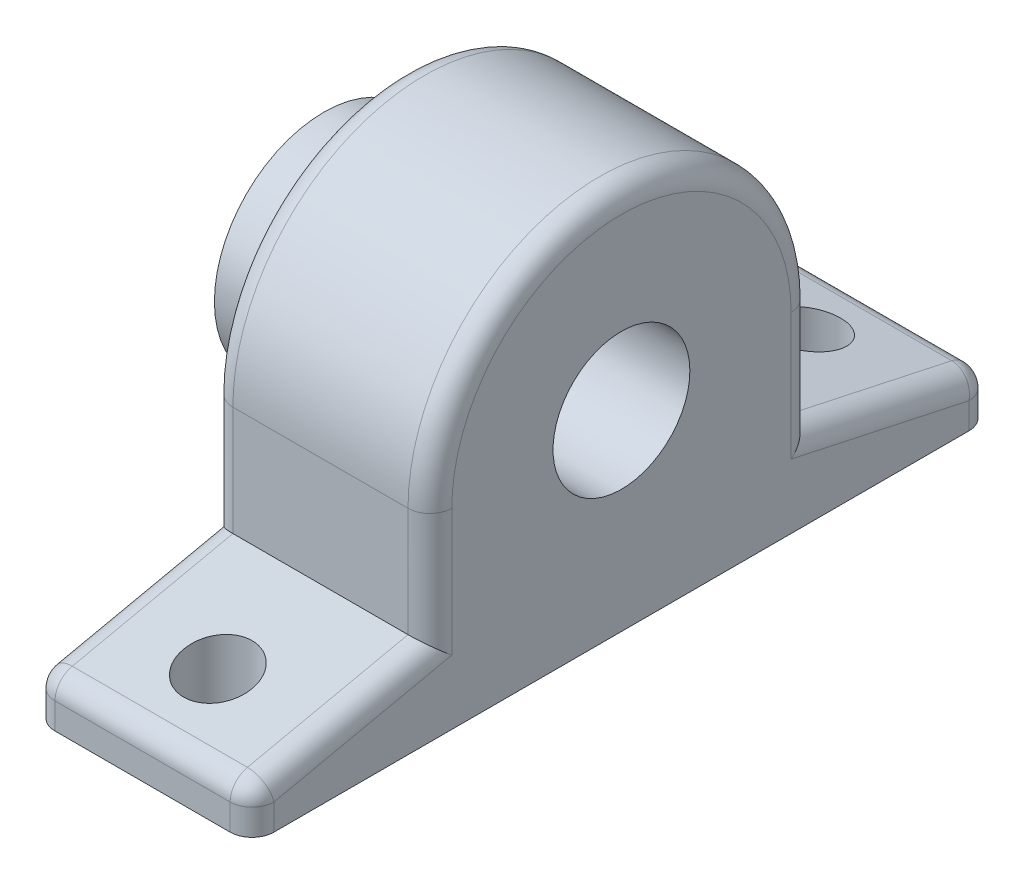
SolidWorks part; units mm, degrees
material "AISI 1020"
ref_plane "Front Plane" through (0, 0, 0) normal (0, 0, 1) x (1, 0, 0)
ref_plane "Top Plane" through (0, 0, 0) normal (0, 1, 0) x (1, 0, 0)
ref_plane "Right Plane" through (0, 0, 0) normal (1, 0, 0) x (0, 0, -1)
sketch "Sketch1" plane through (0, 0, 0) normal (1, 0, 0) x (0, 0, -1)
  line L0 (22.225, 0) -> (22.225, -12.7)
  line L1 (-42.8625, -22.225) -> (42.8625, -22.225)
  line L3 (22.225, -12.7) -> (22.2011, -13.0472)
  line L4 (-22.225, 0) -> (-22.225, -12.7)
  line L5 (42.8625, -22.225) -> (42.8625, -17.145)
  line L6 (-42.8625, -22.225) -> (-42.8625, -17.145)
  line L7 (-42.8625, -17.145) -> (-22.225, -12.7)
  line L8 (22.225, -12.7) -> (42.8625, -17.145)
  line L9 (42.8625, -17.145) -> (43.2049, -17.2391)
  arc A1 (-22.225, 0) -> (22.225, 0) centre (0, 0) cw
extrude "Extrude1" add sketch "Sketch1" along normal blind 25.4
sketch "Sketch2" plane through (25.4, 0, 0) normal (1, 0, 0) x (0, 0, -1)
  circle A0 centre (0, 0) radius 7.9375
extrude "Cut-Extrude1" cut sketch "Sketch2" against normal blind 25.4
fillet "Fillet1" radius 2.54 1 edges at (25.4, -14.9225, 32.5437)
fillet "Fillet2" radius 2.54 3 edges at (25.4, -20.9841, 42.8625) (24.6561, -17.906, 42.8625) (11.43, -17.145, 42.8625)
fillet "Fillet3" radius 2.54 3 edges at (25.4, -6.35, -22.225) (25.4, 22.225, 0) (25.4, -7.6491, 22.225)
fillet "Fillet4" radius 2.54 3 edges at (0, -6.35, 22.225) (0, -6.35, -22.225) (0, 22.225, 0)
fillet "Fillet5" radius 2.54 3 edges at (0, -20.7106, 42.8625) (0, -17.6004, 42.2986) (0, -14.433, 30.2712)
fillet "Fillet6" radius 2.54 1 edges at (0, -14.649, -31.2737)
fillet "Fillet7" radius 2.54 3 edges at (0, -20.9841, -42.8625) (0.7439, -17.906, -42.8625) (13.97, -17.145, -42.8625)
fillet "Fillet8" radius 2.54 3 edges at (25.4, -20.7106, -42.8625) (25.4, -17.6004, -42.2986) (25.4, -14.433, -30.2712)
sketch "Sketch3" plane through (0, -22.225, 0) normal (0, -1, 0) x (1, 0, 0)
  line L0 (0, 0) -> (25.4, 0) construction
  line L3 (0, -40.3225) -> (0, 40.3225) construction
  line L4 (25.4, -40.3225) -> (25.4, 40.3225) construction
  line L5 (12.7, 42.8625) -> (12.7, -42.8625) construction
  line L6 (22.86, 42.8625) -> (2.54, 42.8625) construction
  line L7 (22.86, -42.8625) -> (2.54, -42.8625) construction
  circle A0 centre (12.7, 34.1313) radius 3.9688
  circle A1 centre (12.7, -34.1313) radius 3.9688
  dimension "D1" = 68.2625
  dimension "D2" = 34.1313
  dimension "D3" = 7.9375
  dimension "D4" = 7.9375
extrude "Cut-Extrude2" cut sketch "Sketch3" against normal blind 12.7
sketch "Sketch4" plane through (0, 0, 0) normal (-1, 0, 0) x (0, 0, 1)
  circle A0 centre (0, 0) radius 7.9375
  circle A1 centre (0, 0) radius 12.7
  dimension "D1" = 15.875
  dimension "D2" = 25.4
extrude "Extrude2" add sketch "Sketch4" along normal blind 9.1281
